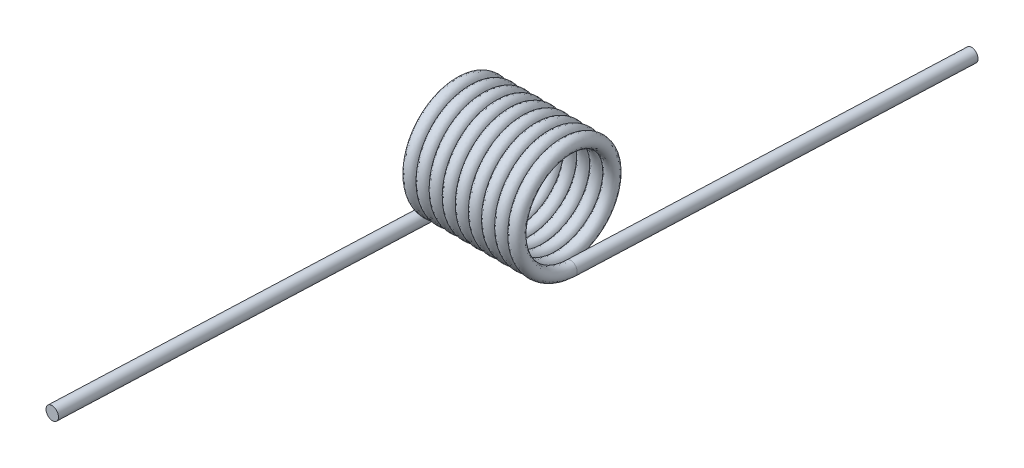
SolidWorks part; units mm, degrees
ref_plane "Front" through (0, 0, 0) normal (0, 0, 1) x (1, 0, 0)
ref_plane "Top" through (0, 0, 0) normal (0, 1, 0) x (1, 0, 0)
ref_plane "Right" through (0, 0, 0) normal (1, 0, 0) x (0, 0, -1)
sketch "Sketch1" plane through (0, 0, 0) normal (1, 0, 0) x (0, 0, -1)
  line L0 (0, 0) -> (0, -11.6713) construction
  line L1 (0, -11.6713) -> (0, -13.3858) construction
  line L2 (0, -13.3858) -> (0, -15.1003) construction
  circle A0 centre (0, 0) radius 11.6713 construction
  circle A1 centre (0, 0) radius 15.1003 construction
  circle A2 centre (0, 0) radius 13.3858
  circle A3 centre (0, -13.3858) radius 1.7145 construction
  circle A4 centre (0, 0) radius 9.3345 construction
  dimension "Wire Dia" = 3.429
  dimension "Spring OD" = 30.2006
  dimension "Max Rod OD" = 18.669
curve "Helix/Spiral1" pitch 3.4544 height 31.0896 radius 13.3858 centre (0, 0, 0) axis (1, 0, 0) start towards (0, 0, -1)
ref_plane "Plane1" through (0, -13.3858, 0) normal (0.041, 0, -0.9992) x (-0.9992, 0, -0.041)
sketch "Sketch2" plane through (0, -13.3858, 0) normal (0.041, 0, -0.9992) x (-0.9992, 0, -0.041)
  circle A0 centre (0, 0) radius 1.7145
  dimension "D1" = 3.429
sweep "Sweep1" add profiles "Sketch2" path "Helix/Spiral1"
sketch "Sketch3" plane through (0, 0, 0) normal (-0.041, 0, 0.9992) x (0.9992, 0, 0.041)
  circle A1 centre (0, -13.3858) radius 1.7145
  circle A2 centre (0, -13.3858) radius 1.7145
  dimension "D1" = 0
extrude "Extrude1" add sketch "Sketch3" along normal blind 101.6
sketch "Sketch4" plane through (0.0524, 0, -1.2748) normal (0.041, 0, -0.9992) x (-0.9955, -0.0856, -0.0409)
  circle A1 centre (-29.8035, -15.9958) radius 1.7145
  circle A2 centre (-29.8035, -15.9958) radius 1.7145
  dimension "D1" = 0
extrude "Extrude2" add sketch "Sketch4" along normal blind 101.6
sketch "Sketch5" plane through (0, 0, 0) normal (1, 0, 0) x (0, 0, -1)
  circle A0 centre (0, 0) radius 9.3345 construction
  circle A1 centre (0, 0) radius 9.3345
equation "\"D4@Helix/Spiral1\"=\"Wire Dia@Sketch1\"+.001"
equation "\"D1@Sketch2\"=\"Wire Dia@Sketch1\""
equation "\"D1@Extrude2\"=\"Leg Length@Extrude1\""
